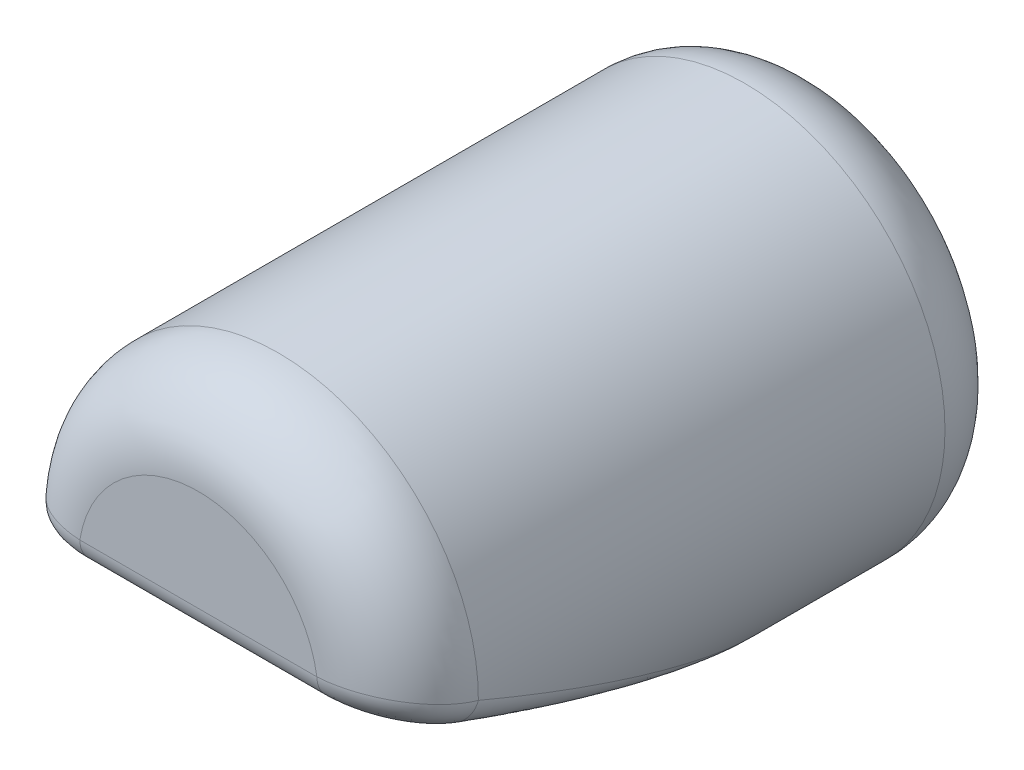
SolidWorks part; units mm, degrees
ref_plane "Front Plane" through (0, 0, 0) normal (0, 0, 1) x (1, 0, 0)
ref_plane "Top Plane" through (0, 0, 0) normal (0, 1, 0) x (1, 0, 0)
ref_plane "Right Plane" through (0, 0, 0) normal (1, 0, 0) x (0, 0, -1)
sketch "Sketch2" plane through (0, 0, 0) normal (0, 0, 1) x (1, 0, 0)
  circle A0 centre (0, 0) radius 7.5
  dimension "D1" = 15
extrude "Boss-Extrude1" add sketch "Sketch2" along normal blind 23.5
ref_point "Point1"
ref_point "Point2"
fillet "Fillet1" radius 3 2 edges at (7.5, 0, 23.5) (7.5, 0, 0)
sketch "Sketch3" plane through (0, 0, 0) normal (1, 0, 0) x (0, 0, -1)
  line L0 (-23.5, 0) -> (-3, -7.5)
  line L1 (-3, -7.5) -> (-3, -10.4048)
  line L2 (-3, -10.4048) -> (-23.5, -10.4048)
  line L3 (-23.5, 0) -> (-23.5, 1000) construction
  line L4 (-23.5, 50) -> (-23.5, -50) construction
  line L5 (-23.5, -10.4048) -> (-23.5, 0)
extrude "Cut-Extrude1" cut sketch "Sketch3" against normal blind 10 and the other way blind 10
fillet "Fillet2" radius 1 5 edges at (4.8999, -5.6781, 7.9799) (6.523, -0.2892, 22.7095) (-4.8999, -5.6781, 7.9799) (-6.8338, -0.4136, 22.3695) (0, 0, 23.5)
